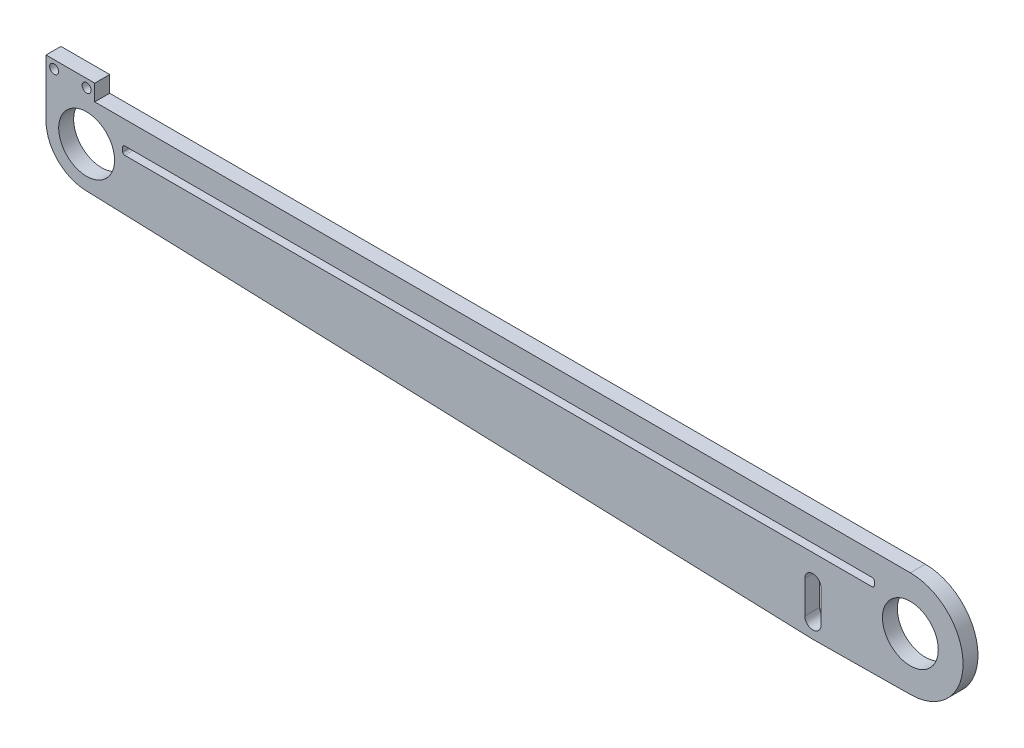
SolidWorks part; units mm, degrees
ref_plane "Front Plane" through (0, 0, 0) normal (0, 0, 1) x (1, 0, 0)
ref_plane "Top Plane" through (0, 0, 0) normal (0, 1, 0) x (1, 0, 0)
ref_plane "Right Plane" through (0, 0, 0) normal (1, 0, 0) x (0, 0, -1)
sketch "Sketch1" plane through (0, 0, 0) normal (0, 0, 1) x (1, 0, 0)
  line L0 (160.7452, 0) -> (-161.2202, 4.7244) construction
  line L1 (160.954, -20.5983) -> (122.6452, -20.9867)
  line L2 (-161.7696, -11.1411) -> (122.6452, -20.9902)
  line L5 (177.8, -25.4) -> (-177.8, 25.4) construction
  line L6 (177.8, 25.4) -> (-177.8, -25.4) construction
  line L7 (-161.2202, 12.573) -> (160.7452, 12.573) construction
  line L8 (177.8, 0) -> (-177.8, 0) construction
  line L9 (160.3763, -12.5676) -> (-161.4504, -3.1208) construction
  line L10 (122.6452, 25.4) -> (122.6452, -25.4) construction
  line L11 (122.6452, -1.9364) -> (122.6452, -14.6364) construction
  line L12 (125.8202, -1.9364) -> (125.8202, -14.6364)
  line L13 (119.4702, -1.9364) -> (119.4702, -14.6364)
  line L14 (-161.2202, 20.5994) -> (160.7452, 20.5994)
  circle A0 centre (-161.2202, 4.7244) radius 7.8486 construction
  circle A1 centre (160.7452, 0) radius 12.573 construction
  arc A2 (125.8202, -1.9364) -> (119.4702, -1.9364) centre (122.6452, -1.9364) ccw
  arc A3 (119.4702, -14.6364) -> (125.8202, -14.6364) centre (122.6452, -14.6364) ccw
  circle A4 centre (-161.2202, 4.7244) radius 10.9125
  circle A5 centre (160.7452, 0) radius 10.9125
  arc A6 (160.954, -20.5983) -> (160.7452, 20.5994) centre (160.7452, 0) ccw
  arc A7 (-161.2202, 20.5994) -> (-161.7696, -11.1411) centre (-161.2202, 4.7244) ccw
  arc A9 (122.4254, -20.9826) -> (122.7096, -20.9861) centre (122.6452, -14.6364) ccw
  point P0 (0, 0)
  point P9 (-0.2375, 2.3622)
  point P21 (122.6452, -8.2864)
  dimension "D4" = 25.146
  dimension "D5" = 15.6972
  dimension "D7" = 3.175
  dimension "D10" = 21.825
  dimension "D11" = 21.825
  dimension "D13" = 31.75
  dimension "D1" = 322
  dimension "D2" = 355.6
  dimension "D3" = 50.8
  dimension "D6" = 38.1
  dimension "D8" = 12.7
  dimension "D9" = 3.175
extrude "Boss-Extrude1" add sketch "Sketch1" along normal blind 5.842 contours L2 A9 L1 A6 L14 A7 A3 L13 A2 L12 A4 A5 region at (9.9688, 1.9104, 0)
sketch "Sketch2" plane through (0, 0, 5.842) normal (0, 0, 1) x (1, 0, 0)
  line L0 (-161.2202, 20.5994) -> (160.7452, 20.5994) construction
  line L1 (-147.1327, 11.557) -> (146.6577, 11.557)
  line L2 (-147.1327, 11.557) -> (-147.1327, 8.382)
  line L3 (-147.1327, 8.382) -> (146.6577, 8.382)
  line L4 (146.6577, 11.557) -> (146.6577, 8.382)
  line L5 (-150.3077, 4.7244) -> (-150.3077, 20.5994) construction
  line L6 (149.8327, 0) -> (149.8327, 20.5994) construction
  circle A0 centre (-161.2202, 4.7244) radius 10.9125 construction
  circle A1 centre (160.7452, 0) radius 10.9125 construction
  dimension "D1" = 3.175
  dimension "D2" = 9.0424
  dimension "D3" = 3.175
  dimension "D4" = 3.175
extrude "Cut-Extrude1" cut sketch "Sketch2" against normal through all
fillet "Fillet1" radius 0.7937 4 edges at (146.6577, 11.557, 2.921) (146.6577, 8.382, 2.921) (-147.1327, 11.557, 2.921) (-147.1327, 8.382, 2.921)
sketch "Sketch3" [suppressed] plane through (0, 0, 5.842) normal (0, 0, 1) x (1, 0, 0)
  circle A0 centre (160.7452, 0) radius 13.97
  dimension "D1" = 27.94
extrude "Cut-Extrude2" [suppressed] cut sketch "Sketch3" against normal through all
sketch "Sketch5" plane through (0, 0, 5.842) normal (0, 0, 1) x (1, 0, 0)
  line L1 (-177.0928, 4.9991) -> (-168.7683, 15.0982)
  line L2 (-177.0952, 20.5994) -> (-177.0952, 26.9494)
  line L3 (-177.0952, 26.9494) -> (-158.0452, 26.9494)
  line L4 (-158.0452, 20.5994) -> (-158.0452, 26.9494)
  line L5 (-177.0952, 20.5994) -> (-158.0452, 26.9494) construction
  line L6 (-177.0952, 26.9494) -> (-158.0452, 20.5994) construction
  line L7 (-177.0928, 4.9991) -> (-177.0952, 20.5994)
  line L8 (-168.7683, 15.0982) -> (-158.0452, 20.5994)
  line L9 (-158.0452, 23.7744) -> (-177.0952, 23.7744) construction
  line L10 (-167.5702, 23.7744) -> (-167.5702, 26.9494) construction
  arc A0 (-161.2202, 20.5994) -> (-161.7696, -11.1411) centre (-161.2202, 4.7244) ccw construction
  circle A2 centre (-173.9202, 23.7744) radius 1.7526
  circle A3 centre (-161.2202, 23.7744) radius 1.7526
  point P0 (-167.5702, 23.7744)
  dimension "D3" = 3.5052
  dimension "D1" = 19.05
  dimension "D2" = 6.35
  dimension "D4" = 6.35
  dimension "D5" = 3.175
extrude "Boss-Extrude3" add sketch "Sketch5" against normal up to surface (5.842 mm away) up to face at (-0.2375, 9.9695, 0)
